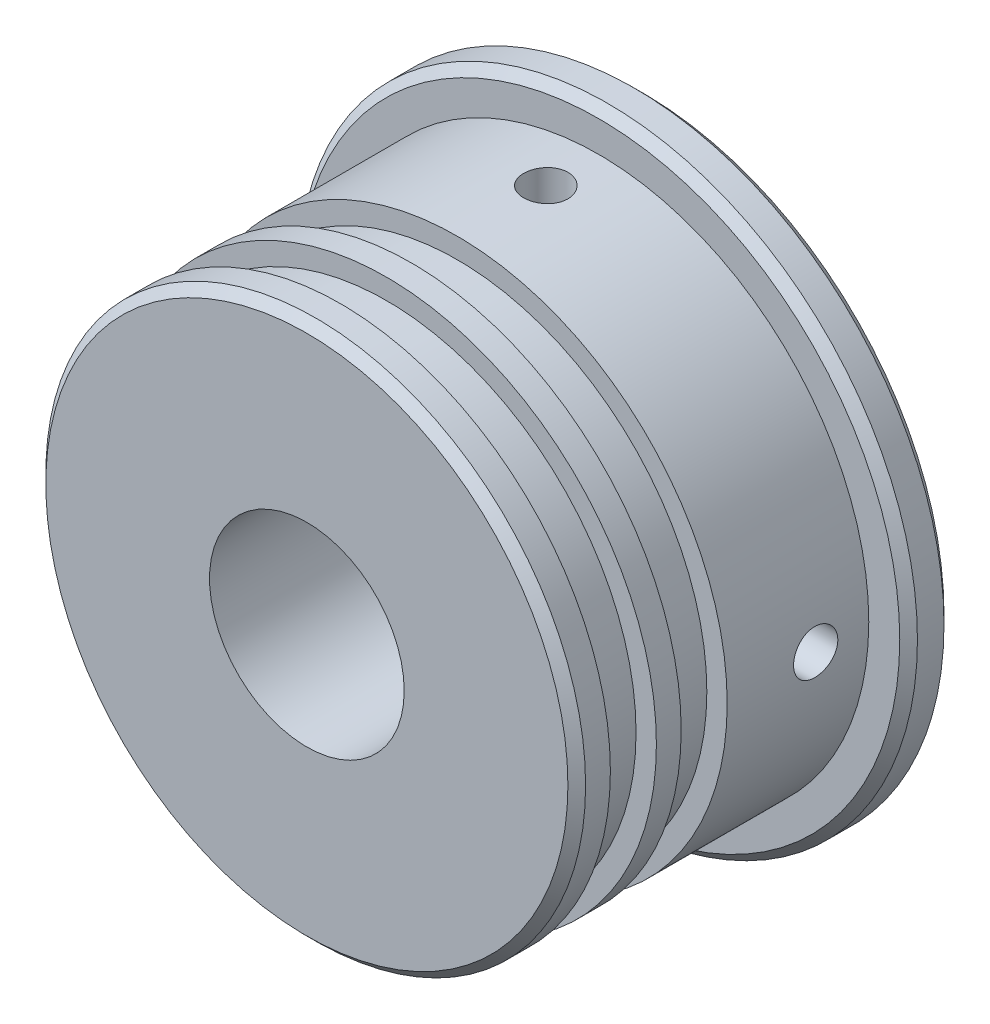
SolidWorks part; units mm, degrees
ref_plane "Спереди" through (0, 0, 0) normal (0, 0, 1) x (1, 0, 0)
ref_plane "Сверху" through (0, 0, 0) normal (0, 1, 0) x (1, 0, 0)
ref_plane "Справа" through (0, 0, 0) normal (1, 0, 0) x (0, 0, -1)
other "Configuration Table"
sketch "Эскиз1" plane through (0, 0, 0) normal (0, 0, 1) x (1, 0, 0)
  circle A0 centre (0, 0) radius 17.5
  circle A1 centre (0, 0) radius 15.25
  circle A2 centre (0, 0) radius 14.1
  circle A3 centre (0, 0) radius 5.5
  dimension "D1" = 35
  dimension "D2" = 30.5
  dimension "D3" = 28.2
  dimension "D4" = 11
extrude "Бобышка-Вытянуть1" add sketch "Эскиз1" against normal blind 2.5 contours A0 A1 | A1 A2 | A2 region at (-17.005, 0, 0) region at (-14.8187, 0, 0) region at (-13.7012, 0, 0)
extrude "Бобышка-Вытянуть2" add sketch "Эскиз1<3>" along normal blind 16.5 contours A1 A2 | A2 region at (-14.8187, 0, 0) region at (-13.7012, 0, 0)
sketch "Эскиз1<3>" plane through (0, 0, 0) normal (0, 0, 1) x (1, 0, 0) same geometry as "Эскиз1"
extrude "Вырез-Вытянуть1" cut sketch "Эскиз1<4>" along normal blind 2.6 from offset 8 contours A1 A2 region at (-14.8187, 0, 0)
sketch "Эскиз1<4>" plane through (0, 0, 0) normal (0, 0, 1) x (1, 0, 0) same geometry as "Эскиз1"
extrude "Вырез-Вытянуть2" cut sketch "Эскиз1<5>" along normal blind 2.6 from offset 12 contours A1 A2 region at (-14.8187, 0, 0)
sketch "Эскиз1<5>" plane through (0, 0, 0) normal (0, 0, 1) x (1, 0, 0) same geometry as "Эскиз1"
chamfer "Фаска1" distance 0.5 angle 45 3 edges at (15.25, 0, 16.5) (17.5, 0, 0) (17.5, 0, -2.5)
sketch "Эскиз2" plane through (0, 0, -2.5) normal (0, 0, -1) x (-1, 0, 0)
  circle A0 centre (0, 0) radius 6
  dimension "D1" = 12
extrude "Вырез-Вытянуть3" cut sketch "Эскиз2" against normal blind 2.5
sketch "Эскиз3" plane through (0, 0, 0) normal (0, 1, 0) x (1, 0, 0)
  line L0 (0, 0) -> (0, 5.0181)
  circle A0 centre (0, -3) radius 1.25
  dimension "D1" = 2.5
  dimension "D2" = 3
extrude "Вырез-Вытянуть4" cut sketch "Эскиз3" along normal blind 10 from offset 10 contours A0 region at (0, 0, 3)
pattern_circular "Круговой массив1" count 4 every 90 about axis through (0, 0, 0) along (0, 0, -1) of "Вырез-Вытянуть4"
